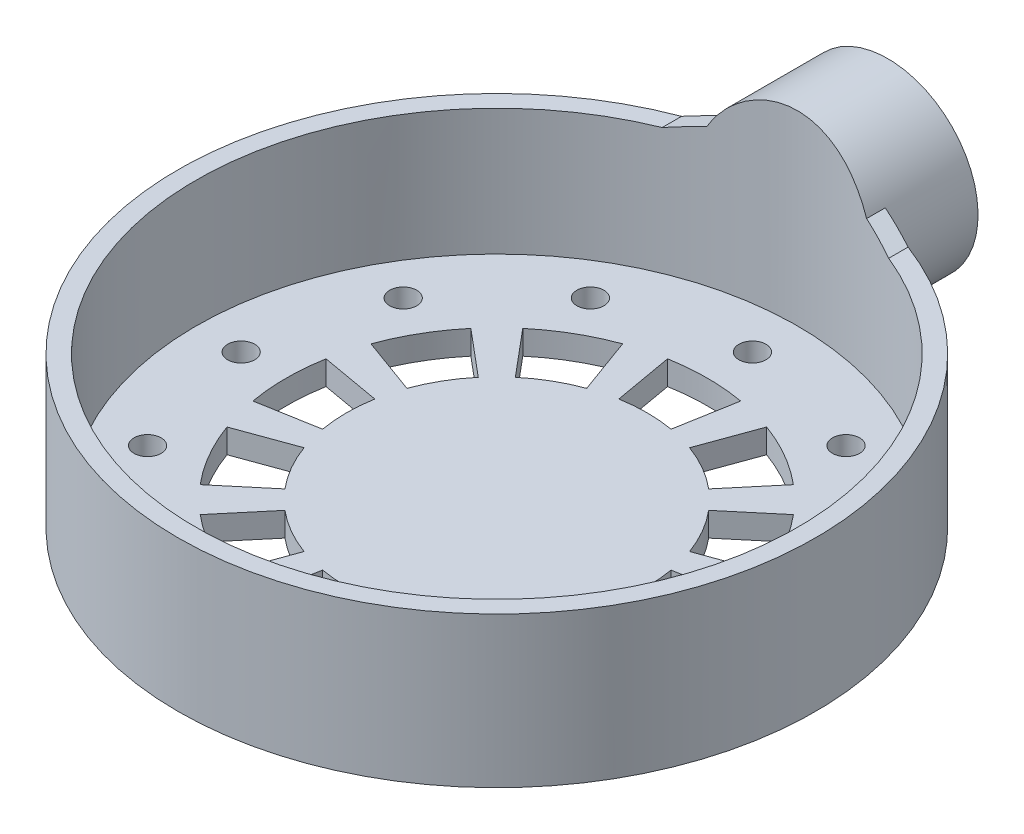
SolidWorks part; units mm, degrees
ref_plane "Спереди" through (0, 0, 0) normal (0, 0, 1) x (1, 0, 0)
ref_plane "Сверху" through (0, 0, 0) normal (0, 1, 0) x (1, 0, 0)
ref_plane "Справа" through (0, 0, 0) normal (1, 0, 0) x (0, 0, -1)
other "Configuration Table"
sketch "Эскиз1" plane through (0, 0, 0) normal (0, 1, 0) x (1, 0, 0)
  circle A0 centre (0, 0) radius 50
  dimension "D1" = 100
extrude "Бобышка-Вытянуть1" add sketch "Эскиз1" along normal blind 4
hole_wizard "Отверстие с зазором M41" positions "Эскиз2" profile "Эскиз3" hole size "M4" standard "DIN" end condition through all
sketch "Эскиз2" plane through (0, 0, 0) normal (0, -1, 0) x (-1, 0, 0)
  circle A0 centre (0, 0) radius 42.5 construction
  point P5 (0, 42.5)
  point P13 (21.25, 36.8061)
  point P14 (36.8061, 21.25)
  point P15 (42.5, 0)
  point P16 (36.8061, -21.25)
  point P17 (21.25, -36.8061)
  point P18 (0, -42.5)
  point P19 (-21.25, -36.8061)
  point P20 (-36.8061, -21.25)
  point P21 (-42.5, 0)
  point P22 (-36.8061, 21.25)
  point P23 (-21.25, 36.8061)
  dimension "D1" = 85
  dimension "D2" = 12
sketch "Эскиз3" plane through (21.25, 0, -36.8061) normal (1, 0, 0) x (0, 0, -1)
  line L0 (0, 0) -> (0, 4)
  line L1 (0, 4) -> (2.25, 4)
  line L2 (2.25, 4) -> (2.25, 0.25)
  line L3 (2.25, 0.25) -> (2.5, 0)
  line L5 (2.5, 0) -> (0, 0)
  line L6 (-2.25, 0.25) -> (-2.5, 0) construction
  line L11 (0, -6.35) -> (0, 107.95) construction
  dimension "Диаметр сквозного отверстия" = 4.5
  dimension "Глубина сквозного отверстия" = 4
  dimension "Диаметр передней зенковки" = 5
  dimension "Угол передней зенковки" = 90
sketch "Эскиз4" plane through (0, 0, 0) normal (0, -1, 0) x (1, 0, 0)
  line L2 (11.9707, 32.8892) -> (8.5505, 23.4923)
  line L3 (16.0697, 19.1511) -> (22.4976, 26.8116)
  line L4 (11.9707, 32.8892) -> (8.5505, 23.4923)
  line L5 (16.0697, 19.1511) -> (22.4976, 26.8116)
  line L6 (-6.0777, 34.4683) -> (-4.3412, 24.6202)
  line L7 (4.3412, 24.6202) -> (6.0777, 34.4683)
  line L8 (-6.0777, 34.4683) -> (-4.3412, 24.6202)
  line L9 (4.3412, 24.6202) -> (6.0777, 34.4683)
  line L10 (32.8892, -11.9707) -> (23.4923, -8.5505)
  line L11 (19.1511, -16.0697) -> (26.8116, -22.4976)
  line L12 (32.8892, -11.9707) -> (23.4923, -8.5505)
  line L13 (19.1511, -16.0697) -> (26.8116, -22.4976)
  line L14 (34.4683, 6.0777) -> (24.6202, 4.3412)
  line L15 (24.6202, -4.3412) -> (34.4683, -6.0777)
  line L16 (34.4683, 6.0777) -> (24.6202, 4.3412)
  line L17 (24.6202, -4.3412) -> (34.4683, -6.0777)
  line L18 (26.8116, 22.4976) -> (19.1511, 16.0697)
  line L19 (23.4923, 8.5505) -> (32.8892, 11.9707)
  line L20 (26.8116, 22.4976) -> (19.1511, 16.0697)
  line L21 (23.4923, 8.5505) -> (32.8892, 11.9707)
  line L22 (-11.9707, -32.8892) -> (-8.5505, -23.4923)
  line L23 (-16.0697, -19.1511) -> (-22.4976, -26.8116)
  line L24 (-11.9707, -32.8892) -> (-8.5505, -23.4923)
  line L25 (-16.0697, -19.1511) -> (-22.4976, -26.8116)
  line L26 (6.0777, -34.4683) -> (4.3412, -24.6202)
  line L27 (-4.3412, -24.6202) -> (-6.0777, -34.4683)
  line L28 (6.0777, -34.4683) -> (4.3412, -24.6202)
  line L29 (-4.3412, -24.6202) -> (-6.0777, -34.4683)
  line L30 (22.4976, -26.8116) -> (16.0697, -19.1511)
  line L31 (8.5505, -23.4923) -> (11.9707, -32.8892)
  line L32 (22.4976, -26.8116) -> (16.0697, -19.1511)
  line L33 (8.5505, -23.4923) -> (11.9707, -32.8892)
  line L34 (-22.4976, 26.8116) -> (-16.0697, 19.1511)
  line L35 (-8.5505, 23.4923) -> (-11.9707, 32.8892)
  line L36 (-22.4976, 26.8116) -> (-16.0697, 19.1511)
  line L37 (-8.5505, 23.4923) -> (-11.9707, 32.8892)
  line L38 (-32.8892, 11.9707) -> (-23.4923, 8.5505)
  line L39 (-19.1511, 16.0697) -> (-26.8116, 22.4976)
  line L40 (-32.8892, 11.9707) -> (-23.4923, 8.5505)
  line L41 (-19.1511, 16.0697) -> (-26.8116, 22.4976)
  line L42 (-34.4683, -6.0777) -> (-24.6202, -4.3412)
  line L43 (-24.6202, 4.3412) -> (-34.4683, 6.0777)
  line L44 (-34.4683, -6.0777) -> (-24.6202, -4.3412)
  line L45 (-24.6202, 4.3412) -> (-34.4683, 6.0777)
  line L46 (-26.8116, -22.4976) -> (-19.1511, -16.0697)
  line L47 (-23.4923, -8.5505) -> (-32.8892, -11.9707)
  line L48 (-26.8116, -22.4976) -> (-19.1511, -16.0697)
  line L49 (-23.4923, -8.5505) -> (-32.8892, -11.9707)
  arc A2 (16.0697, 19.1511) -> (8.5505, 23.4923) centre (0, 0) ccw
  arc A3 (22.4976, 26.8116) -> (11.9707, 32.8892) centre (0, 0) ccw
  arc A4 (16.0697, 19.1511) -> (8.5505, 23.4923) centre (0, 0) ccw
  arc A5 (22.4976, 26.8116) -> (11.9707, 32.8892) centre (0, 0) ccw
  arc A6 (4.3412, 24.6202) -> (-4.3412, 24.6202) centre (0, 0) ccw
  arc A7 (6.0777, 34.4683) -> (-6.0777, 34.4683) centre (0, 0) ccw
  arc A8 (4.3412, 24.6202) -> (-4.3412, 24.6202) centre (0, 0) ccw
  arc A9 (6.0777, 34.4683) -> (-6.0777, 34.4683) centre (0, 0) ccw
  arc A10 (19.1511, -16.0697) -> (23.4923, -8.5505) centre (0, 0) ccw
  arc A11 (26.8116, -22.4976) -> (32.8892, -11.9707) centre (0, 0) ccw
  arc A12 (19.1511, -16.0697) -> (23.4923, -8.5505) centre (0, 0) ccw
  arc A13 (26.8116, -22.4976) -> (32.8892, -11.9707) centre (0, 0) ccw
  arc A14 (24.6202, -4.3412) -> (24.6202, 4.3412) centre (0, 0) ccw
  arc A15 (34.4683, -6.0777) -> (34.4683, 6.0777) centre (0, 0) ccw
  arc A16 (24.6202, -4.3412) -> (24.6202, 4.3412) centre (0, 0) ccw
  arc A17 (34.4683, -6.0777) -> (34.4683, 6.0777) centre (0, 0) ccw
  arc A18 (23.4923, 8.5505) -> (19.1511, 16.0697) centre (0, 0) ccw
  arc A19 (32.8892, 11.9707) -> (26.8116, 22.4976) centre (0, 0) ccw
  arc A20 (23.4923, 8.5505) -> (19.1511, 16.0697) centre (0, 0) ccw
  arc A21 (32.8892, 11.9707) -> (26.8116, 22.4976) centre (0, 0) ccw
  arc A22 (-16.0697, -19.1511) -> (-8.5505, -23.4923) centre (0, 0) ccw
  arc A23 (-22.4976, -26.8116) -> (-11.9707, -32.8892) centre (0, 0) ccw
  arc A24 (-16.0697, -19.1511) -> (-8.5505, -23.4923) centre (0, 0) ccw
  arc A25 (-22.4976, -26.8116) -> (-11.9707, -32.8892) centre (0, 0) ccw
  arc A26 (-4.3412, -24.6202) -> (4.3412, -24.6202) centre (0, 0) ccw
  arc A27 (-6.0777, -34.4683) -> (6.0777, -34.4683) centre (0, 0) ccw
  arc A28 (-4.3412, -24.6202) -> (4.3412, -24.6202) centre (0, 0) ccw
  arc A29 (-6.0777, -34.4683) -> (6.0777, -34.4683) centre (0, 0) ccw
  arc A30 (11.9707, -32.8892) -> (22.4976, -26.8116) centre (0, 0) ccw
  arc A31 (8.5505, -23.4923) -> (16.0697, -19.1511) centre (0, 0) ccw
  arc A32 (11.9707, -32.8892) -> (22.4976, -26.8116) centre (0, 0) ccw
  arc A33 (8.5505, -23.4923) -> (16.0697, -19.1511) centre (0, 0) ccw
  arc A34 (-8.5505, 23.4923) -> (-16.0697, 19.1511) centre (0, 0) ccw
  arc A35 (-11.9707, 32.8892) -> (-22.4976, 26.8116) centre (0, 0) ccw
  arc A36 (-8.5505, 23.4923) -> (-16.0697, 19.1511) centre (0, 0) ccw
  arc A37 (-11.9707, 32.8892) -> (-22.4976, 26.8116) centre (0, 0) ccw
  arc A38 (-19.1511, 16.0697) -> (-23.4923, 8.5505) centre (0, 0) ccw
  arc A39 (-26.8116, 22.4976) -> (-32.8892, 11.9707) centre (0, 0) ccw
  arc A40 (-19.1511, 16.0697) -> (-23.4923, 8.5505) centre (0, 0) ccw
  arc A41 (-26.8116, 22.4976) -> (-32.8892, 11.9707) centre (0, 0) ccw
  arc A42 (-24.6202, 4.3412) -> (-24.6202, -4.3412) centre (0, 0) ccw
  arc A43 (-34.4683, 6.0777) -> (-34.4683, -6.0777) centre (0, 0) ccw
  arc A44 (-24.6202, 4.3412) -> (-24.6202, -4.3412) centre (0, 0) ccw
  arc A45 (-34.4683, 6.0777) -> (-34.4683, -6.0777) centre (0, 0) ccw
  arc A46 (-32.8892, -11.9707) -> (-26.8116, -22.4976) centre (0, 0) ccw
  arc A47 (-23.4923, -8.5505) -> (-19.1511, -16.0697) centre (0, 0) ccw
  arc A48 (-32.8892, -11.9707) -> (-26.8116, -22.4976) centre (0, 0) ccw
  arc A49 (-23.4923, -8.5505) -> (-19.1511, -16.0697) centre (0, 0) ccw
  dimension "D1" = 0
  dimension "D2" = 0
  dimension "D3" = 0
  dimension "D4" = 0
  dimension "D5" = 0
  dimension "D6" = 0
  dimension "D7" = 0
  dimension "D8" = 0
  dimension "D9" = 0
  dimension "D10" = 0
  dimension "D11" = 0
  dimension "D12" = 0
extrude "Вырез-Вытянуть1" cut sketch "Эскиз4" against normal through all
sketch "Эскиз5" plane through (0, 0, 0) normal (0, -1, 0) x (1, 0, 0)
  circle A0 centre (0, 0) radius 53
  circle A1 centre (0, 0) radius 50 construction
  circle A2 centre (0, 0) radius 50
  dimension "D1" = 3
extrude "Бобышка-Вытянуть2" add sketch "Эскиз5" against normal blind 25
ref_plane "Плоскость1" through (0, 0, -53) normal (0, 0, -1) x (-1, 0, 0)
sketch "Эскиз6" plane through (0, 0, -53) normal (0, 0, -1) x (-1, 0, 0)
  circle A0 centre (0, 20) radius 15 construction
  circle A1 centre (0, 20) radius 15
extrude "Бобышка-Вытянуть3" add sketch "Эскиз6" against normal up to surface and the other way up to surface (12 mm away) up to face at (0, 4, 50)
chamfer "Фаска1" distance 3 angle 45 2 edges at (-14.1421, 25, -49.5183) (14.1421, 25, -49.5183)
